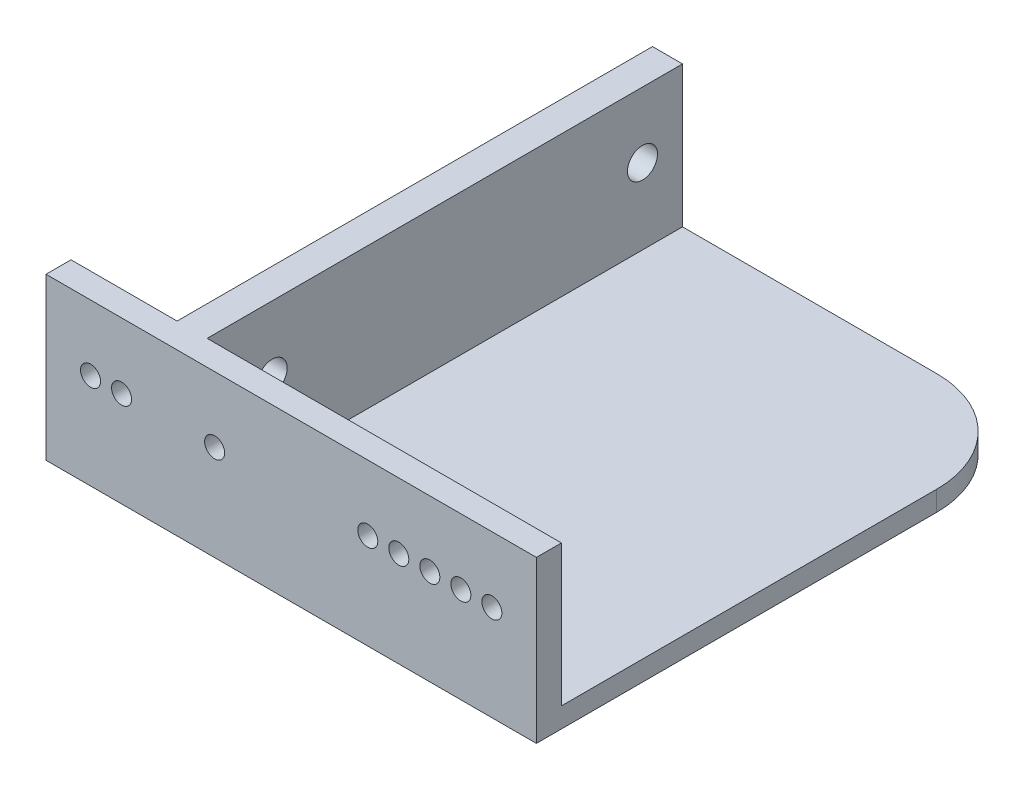
SolidWorks part; units mm, degrees
ref_plane "Front Plane" through (0, 0, 0) normal (0, 0, 1) x (1, 0, 0)
ref_plane "Top Plane" through (0, 0, 0) normal (0, 1, 0) x (1, 0, 0)
ref_plane "Right Plane" through (0, 0, 0) normal (1, 0, 0) x (0, 0, -1)
sketch "Sketch1" plane through (0, 0, 0) normal (1, 0, 0) x (0, 0, -1)
  line L1 (0, 0) -> (50, 0)
  line L2 (0, 0) -> (0, 16.1)
  line L3 (0, 16.1) -> (50, 16.1)
  line L4 (50, 0) -> (50, 16.1)
  dimension "D1" = 50
  dimension "D2" = 16.1
extrude "Boss-Extrude1" add sketch "Sketch1" along normal blind 3
sketch "Sketch3" plane through (3, 0, 0) normal (1, 0, 0) x (0, 0, -1)
  line L0 (0, 9.55) -> (50, 9.55) construction
  line L2 (50, 0) -> (50, 16.1) construction
  line L3 (50, 16.1) -> (0, 16.1) construction
  circle A0 centre (46, 9.55) radius 1.5
  circle A1 centre (9, 9.55) radius 1.5
  dimension "D1" = 37
  dimension "D2" = 4
  dimension "D3" = 3
  dimension "D4" = 6.55
extrude "Cut-Extrude1" cut sketch "Sketch3" against normal through all
sketch "Sketch4" plane through (3, 0, 0) normal (1, 0, 0) x (0, 0, -1)
  line L0 (50, 16.1) -> (0, 16.1) construction
  line L1 (0, 0) -> (2.5, 0)
  line L2 (0, 0) -> (0, 16.1)
  line L3 (0, 16.1) -> (2.5, 16.1)
  line L4 (2.5, 0) -> (2.5, 16.1)
  dimension "D1" = 2.5
extrude "Boss-Extrude2" add sketch "Sketch4" along normal blind 35.4 and the other way blind 13.6
sketch "Sketch6" plane through (0, 0, -2.5) normal (0, 0, -1) x (-1, 0, 0)
  line L0 (10.6, 9.55) -> (-38.4, 9.55) construction
  line L1 (-3, 16.1) -> (-3, 0) construction
  line L2 (10.6, 0) -> (10.6, 16.1) construction
  line L3 (-38.4, 16.1) -> (-3, 16.1) construction
  line L4 (-38.4, 0) -> (-38.4, 16.1) construction
  circle A0 centre (6.15, 9.55) radius 1
  circle A1 centre (3.05, 9.55) radius 1
  circle A2 centre (-0.05, 9.55) radius 1 construction
  circle A3 centre (-3.15, 9.55) radius 1 construction
  circle A4 centre (-6.25, 9.55) radius 1
  circle A5 centre (-21.55, 9.55) radius 1
  circle A6 centre (-24.65, 9.55) radius 1
  circle A7 centre (-27.75, 9.55) radius 1
  circle A8 centre (-30.85, 9.55) radius 1
  circle A9 centre (-33.95, 9.55) radius 1
  dimension "D1" = 2
  dimension "D2" = 18.55
  dimension "D4" = 15.3
  dimension "D6" = 6.55
  dimension "D3" = 5
  dimension "D5" = 5
extrude "Cut-Extrude2" cut sketch "Sketch6" against normal blind 45
sketch "Sketch10" plane through (0, 0, -2.5) normal (0, 0, -1) x (-1, 0, 0)
  line L0 (10.6, 0) -> (10.6, 16.1) construction
  line L1 (-38.4, 0) -> (10.6, 0)
  line L2 (-38.4, 0) -> (-38.4, 2)
  line L3 (-38.4, 2) -> (10.6, 2)
  line L4 (10.6, 0) -> (10.6, 2)
  dimension "D1" = 2
extrude "Boss-Extrude4" add sketch "Sketch10" along normal up to surface (47.5 mm away) up to face at (1.5, 8.05, -50)
fillet "Fillet1" radius 10 1 edges at (38.4, 1, -50)
sketch "Sketch8" plane through (2.5, 0, 0) normal (1, 0, 0) x (0, 0, -1)
  line L0 (2.5, 0) -> (2.5, 15.1) construction
  line L1 (2.5, 2) -> (50, 2)
  line L2 (2.5, 2) -> (2.5, 0)
  line L3 (2.5, 0) -> (50, 0)
  line L4 (50, 2) -> (50, 0)
  dimension "D1" = 2
extrude "Boss-Extrude3" [suppressed] add sketch "Sketch8" along normal up to surface (50 mm away) up to face at (38.4, 6.0333, -14.1667)
sketch "Sketch9" [suppressed] plane through (0, 2, 0) normal (0, 1, 0) x (1, 0, 0)
  line L0 (45.2405, 2.5) -> (2.5, 43.1034)
  line L1 (52.5, 2.5) -> (2.5, 2.5) construction
  line L2 (2.5, 50) -> (2.5, 2.5) construction
  line L3 (52.5, 2.5) -> (2.5, 50)
  line L4 (17.5, 2.5) -> (2.5, 16.75)
  line L5 (2.5, 43.1034) -> (2.5, 23.6466)
  line L6 (2.5, 23.6466) -> (24.7595, 2.5)
  line L7 (24.7595, 2.5) -> (45.2405, 2.5)
  line L8 (17.5, 2.5) -> (2.5, 2.5)
  line L9 (2.5, 2.5) -> (2.5, 16.75)
  line L10 (52.5, 2.5) -> (52.5, 50)
  line L11 (52.5, 2.5) -> (52.5, 50) construction
  line L12 (52.5, 50) -> (2.5, 50) construction
  line L13 (52.5, 50) -> (2.5, 50)
  dimension "D1" = 5
  dimension "D2" = 5
  dimension "D3" = 15
extrude "Cut-Extrude3" [suppressed] cut sketch "Sketch9" against normal through all
